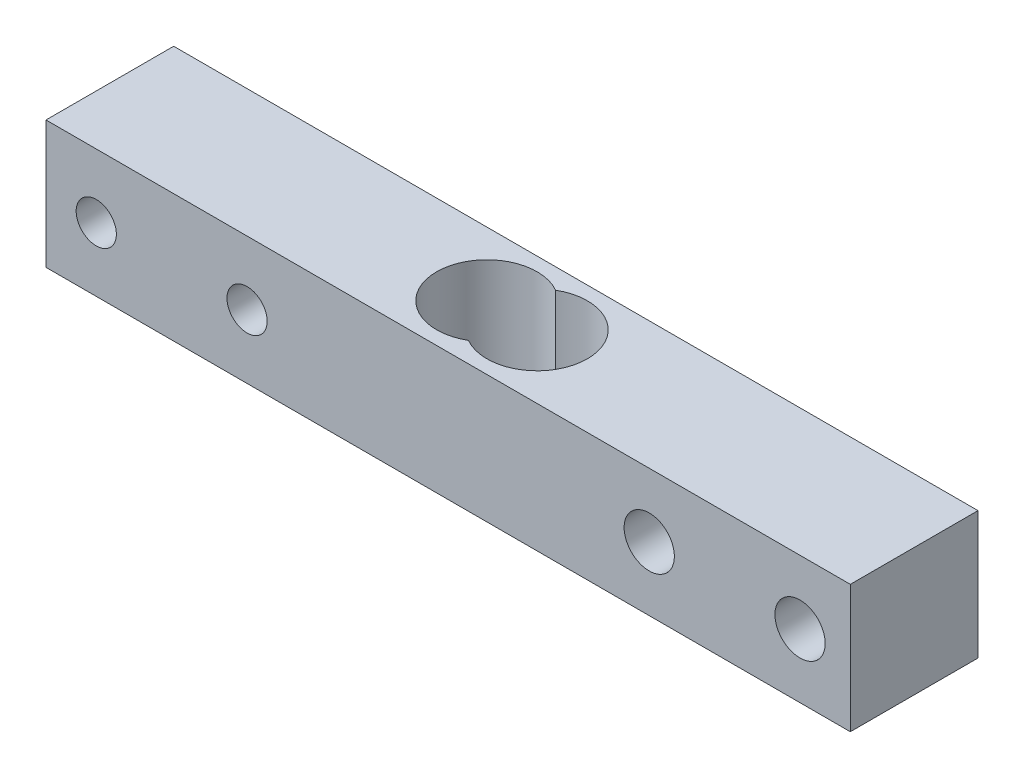
SolidWorks part; units mm, degrees
ref_plane "Front" through (0, 0, 0) normal (0, 0, 1) x (1, 0, 0)
ref_plane "Top" through (0, 0, 0) normal (0, 1, 0) x (1, 0, 0)
ref_plane "Right" through (0, 0, 0) normal (1, 0, 0) x (0, 0, -1)
sketch "Çizim1" plane through (0, 0, 0) normal (0, 0, 1) x (1, 0, 0)
  line L1 (-40, 6.35) -> (40, 6.35)
  line L2 (-40, 6.35) -> (-40, -6.35)
  line L3 (-40, -6.35) -> (40, -6.35)
  line L4 (40, 6.35) -> (40, -6.35)
  line L5 (-40, 6.35) -> (40, -6.35) construction
  line L6 (-40, -6.35) -> (40, 6.35) construction
  point P0 (0, 0)
  dimension "D1" = 80
  dimension "D2" = 12.7
extrude "Yükseklik-Ekstrüzyon1" add sketch "Çizim1" along normal blind 12.7
sketch "Çizim2" plane through (0, 0, 12.7) normal (0, 0, 1) x (1, 0, 0)
  line L0 (40, 0) -> (35, 0)
  line L1 (40, -6.35) -> (40, 6.35) construction
  line L2 (35, 0) -> (20, 0)
  line L3 (-40, 0) -> (-35, 0)
  line L4 (-40, 6.35) -> (-40, -6.35) construction
  line L5 (-35, 0) -> (-20, 0)
  circle A0 centre (35, 0) radius 2.5
  circle A1 centre (20, 0) radius 2.5
  circle A2 centre (-35, 0) radius 2
  circle A3 centre (-20, 0) radius 2
  dimension "D1" = 15
  dimension "D2" = 5
  dimension "D3" = 5
  dimension "D4" = 15
extrude "Kes-Ekstrüzyon1" cut sketch "Çizim2" against normal blind 12.7 contours L3 A2 L5 | L5 A2 L3 | A3 | A1 | L2 A0 L0 | L0 A0 L2 region at (35, -1.061, 12.7) region at (35, 1.061, 12.7) region at (17.5707, 0, 12.7) region at (-35, 0.8488, 12.7) region at (-20, 1.9434, 12.7) region at (-35, -0.8488, 12.7)
sketch "Çizim3" plane through (0, 6.35, 0) normal (0, 1, 0) x (1, 0, 0)
  line L0 (0, 0) -> (0, -2.0199) construction
  line L1 (40, -12.7) -> (-40, -12.7) construction
  line L4 (0, -10.6801) -> (0, -12.7) construction
  arc A0 (0, -2.0199) -> (0, -10.6801) centre (-2.5, -6.35) ccw
  arc A1 (0, -10.6801) -> (0, -2.0199) centre (2.5, -6.35) ccw
extrude "Kes-Ekstrüzyon2" cut sketch "Çizim3" against normal blind 19.7
